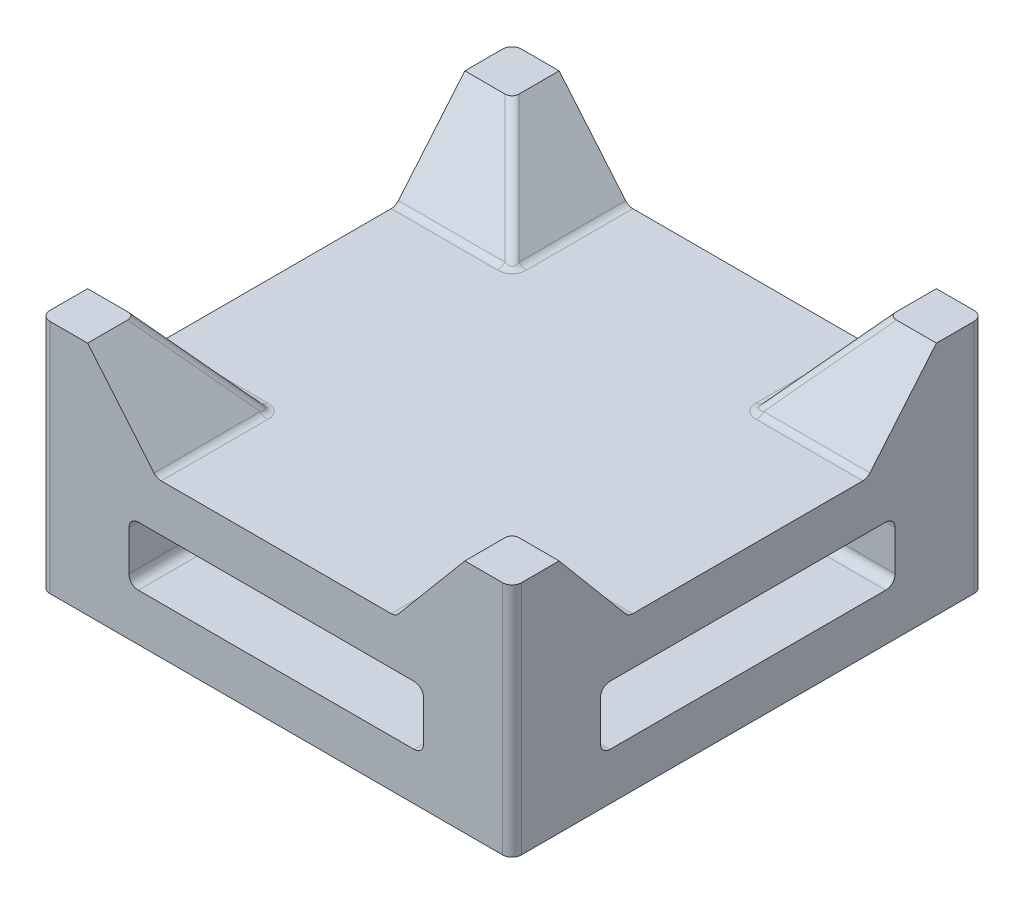
SolidWorks part; units mm, degrees
ref_plane "Front" through (0, 0, 0) normal (0, 0, 1) x (1, 0, 0)
ref_plane "Top" through (0, 0, 0) normal (0, 1, 0) x (1, 0, 0)
ref_plane "Right" through (0, 0, 0) normal (1, 0, 0) x (0, 0, -1)
sketch "Sketch1" plane through (0, 0, 0) normal (0, 1, 0) x (1, 0, 0)
  line L1 (12.7, -12.7) -> (-12.7, -12.7)
  line L2 (12.7, -12.7) -> (12.7, 12.7)
  line L3 (12.7, 12.7) -> (-12.7, 12.7)
  line L4 (-12.7, -12.7) -> (-12.7, 12.7)
  line L5 (12.7, -12.7) -> (-12.7, 12.7) construction
  line L6 (12.7, 12.7) -> (-12.7, -12.7) construction
  point P0 (0, 0)
  dimension "D1" = 25.4
extrude "Boss-Extrude1" add sketch "Sketch1" along normal blind 12.7
sketch "Sketch2" plane through (0, 0, 0) normal (0, 0, 1) x (1, 0, 0)
  line L0 (-10.16, 12.7) -> (-6.4302, 8.255)
  line L1 (-12.7, 12.7) -> (12.7, 12.7) construction
  line L2 (-6.4302, 8.255) -> (6.4302, 8.255)
  line L3 (6.4302, 8.255) -> (10.16, 12.7)
  line L4 (-6.4302, 8.255) -> (-12.7, 8.255) construction
  line L5 (-12.7, 12.7) -> (-12.7, 0) construction
  line L6 (6.4302, 8.255) -> (12.7, 8.255) construction
  line L7 (12.7, 12.7) -> (12.7, 0) construction
  line L8 (-7.9375, 5.715) -> (-12.7, 5.715) construction
  line L9 (-7.9375, 5.715) -> (7.9375, 5.715)
  line L10 (-7.9375, 5.715) -> (-7.9375, 2.54)
  line L11 (-7.9375, 2.54) -> (7.9375, 2.54)
  line L12 (7.9375, 5.715) -> (7.9375, 2.54)
  line L13 (7.9375, 5.715) -> (12.7, 5.715) construction
  line L14 (-12.7, 0) -> (12.7, 0) construction
  line L15 (-10.16, 12.7) -> (10.16, 12.7)
  dimension "D1" = 50
  dimension "D2" = 3.175
  dimension "D3" = 2.54
  dimension "D4" = 2.54
  dimension "D5" = 2.54
  dimension "D6" = 15.875
extrude "Cut-Extrude1" cut sketch "Sketch2" against normal through all both and the other way through all
sketch "Sketch3" plane through (0, 0, 0) normal (1, 0, 0) x (0, 0, -1)
  line L0 (-10.16, 12.7) -> (-6.4302, 8.255)
  line L1 (-7.9375, 5.715) -> (7.9375, 5.715)
  line L2 (-7.9375, 5.715) -> (-7.9375, 2.54)
  line L3 (-7.9375, 2.54) -> (7.9375, 2.54)
  line L4 (7.9375, 5.715) -> (7.9375, 2.54)
  line L5 (-12.7, 12.7) -> (12.7, 12.7) construction
  line L6 (-6.4302, 8.255) -> (6.4302, 8.255)
  line L7 (6.4302, 8.255) -> (10.16, 12.7)
  line L8 (-12.7, 12.7) -> (-12.7, 0) construction
  line L14 (-10.16, 12.7) -> (10.16, 12.7)
  dimension "D1" = 50
  dimension "D2" = 2.54
  dimension "D3" = 15.875
extrude "Cut-Extrude2" cut sketch "Sketch3" against normal through all both and the other way through all
sketch "Sketch4" plane through (0, 0, 0) normal (0, 0, 1) x (1, 0, 0)
  line L0 (-6.35, -3.175) -> (6.35, -3.175)
  line L1 (6.35, -3.175) -> (6.35, -4.7625)
  line L2 (6.35, -4.7625) -> (3.175, -7.9375)
  line L3 (3.175, -7.9375) -> (-3.175, -7.9375)
  line L4 (-3.175, -7.9375) -> (-6.35, -4.7625)
  line L5 (-6.35, -4.7625) -> (-6.35, -3.175)
  line L6 (0, 0) -> (0, -3.175) construction
  line L7 (-12.7, 0) -> (12.7, 0) construction
  dimension "D1" = 12.7
  dimension "D2" = 7.9375
  dimension "D3" = 3.175
  dimension "D4" = 45
  dimension "D5" = 3.175
extrude "Boss-Extrude2" add sketch "Sketch4" along normal mid plane 6.35 separate body
sketch "Sketch5" plane through (0, 0, 0) normal (0, -1, 0) x (1, 0, 0)
  line L0 (-3.175, 3.175) -> (3.175, 3.175) construction
  line L1 (3.175, -3.175) -> (0, -3.175)
  line L2 (3.175, -3.175) -> (3.175, 0)
  line L3 (0, 3.175) -> (-3.175, 3.175)
  line L4 (-3.175, 0) -> (-3.175, 3.175)
  line L5 (3.175, -3.175) -> (-3.175, 3.175) construction
  line L6 (3.175, 3.175) -> (-3.175, -3.175) construction
  arc A0 (0, -3.175) -> (-3.175, 0) centre (0, 0) cw
  arc A1 (3.175, 0) -> (0, 3.175) centre (0, 0) ccw
  point P0 (0, 0)
extrude "Boss-Extrude3" add sketch "Sketch5" along normal up to next
fillet "Fillet1" radius 1.27 4 edges at (7.9375, 4.1275, 7.9375) (7.9375, 4.1275, -7.9375) (-7.9375, 4.1275, -7.9375) (-7.9375, 4.1275, 7.9375)
fillet "Fillet2" radius 0.508 40 edges at (6.4302, 8.255, 9.5651) (9.5651, 8.255, -6.4302) (-6.4302, 8.255, -9.5651) (-9.5651, 8.255, 6.4302) (-7.9375, 5.715, 10.9537) (-10.9538, 5.715, 7.9375) (-10.9538, 2.54, 7.9375) (-7.9375, 2.54, 10.9537) (-7.9375, 2.54, -10.9538) (-10.9538, 2.54, -7.9375) (-10.9538, 5.715, -7.9375) (-7.9375, 5.715, -10.9538) (7.9375, 5.715, -10.9538) (10.9537, 5.715, -7.9375) (10.9537, 2.54, -7.9375) (7.9375, 2.54, -10.9537) (7.9375, 2.54, 10.9537) (10.9537, 2.54, 7.9375) (10.9537, 5.715, 7.9375) (7.9375, 5.715, 10.9537) (-8.3095, 5.715, 8.3095) (-8.3095, 2.54, 8.3095) (-8.3095, 2.54, -8.3095) (-8.3095, 5.715, -8.3095) (8.3095, 5.715, -8.3095) (8.3095, 2.54, -8.3095) (8.3095, 2.54, 8.3095) (8.3095, 5.715, 8.3095) (12.7, 6.35, 12.7) (-12.7, 6.35, 12.7) (12.7, 6.35, -12.7) (-12.7, 6.35, -12.7) (9.5651, 8.255, 6.4302) (8.2951, 10.4775, 8.2951) (6.4302, 8.255, -9.5651) (8.2951, 10.4775, -8.2951) (-9.5651, 8.255, -6.4302) (-8.2951, 10.4775, -8.2951) (-6.4302, 8.255, 9.5651) (-8.2951, 10.4775, 8.2951)
fillet "Fillet3" radius 0.762 10 edges at (3.175, -3.175, -1.5875) (-3.175, -3.175, 1.5875) (-3.175, 0, 1.5875) (1.5875, 0, -3.175) (3.175, 0, -1.5875) (-1.5875, 0, 3.175) (2.2451, -3.175, 2.2451) (-2.2451, -3.175, -2.2451) (-2.2451, 0, -2.2451) (2.2451, 0, 2.2451)
